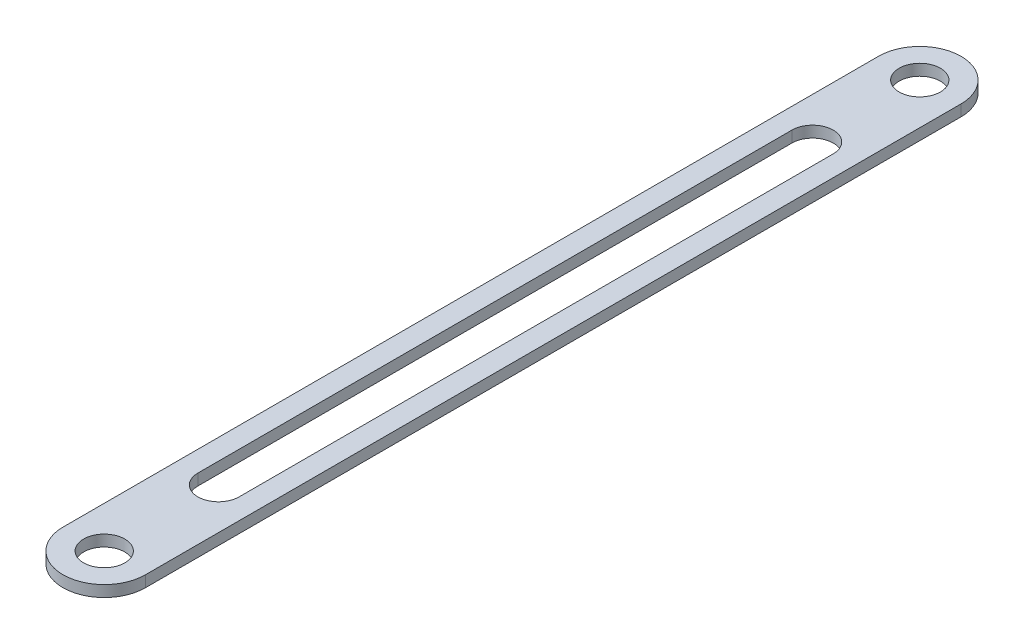
SolidWorks part; units mm, degrees
ref_plane "Front Plane" through (0, 0, 0) normal (0, 0, 1) x (1, 0, 0)
ref_plane "Top Plane" through (0, 0, 0) normal (0, 1, 0) x (1, 0, 0)
ref_plane "Right Plane" through (0, 0, 0) normal (1, 0, 0) x (0, 0, -1)
sketch "Sketch1" plane through (0, 0, 0) normal (0, 1, 0) x (1, 0, 0)
  line L0 (0, 100.4327) -> (0, -254.7867) construction
  line L1 (-11, 23.0454) -> (-11, -194.4046)
  line L2 (11, 23.0454) -> (11, -194.4046)
  line L3 (-67.2169, 0) -> (68.628, 0) construction
  line L4 (-5.5, -5.5346) -> (-5.5, -163.9346)
  line L5 (5.5, -5.5346) -> (5.5, -163.9346)
  arc A0 (-11, 23.0454) -> (11, 23.0454) centre (0, 23.0454) cw
  arc A1 (-11, -194.4046) -> (11, -194.4046) centre (0, -194.4046) ccw
  circle A2 centre (0, 23.0454) radius 5.5
  circle A3 centre (0, -194.4046) radius 5.5
  arc A4 (-5.5, -5.5346) -> (5.5, -5.5346) centre (0, -5.5346) cw
  arc A5 (-5.5, -163.9346) -> (5.5, -163.9346) centre (0, -163.9346) ccw
  point P19 (0, -0.0346)
  point P20 (0, -169.4346)
  dimension "D1" = 11
  dimension "D2" = 11
  dimension "D3" = 11
  dimension "D6" = 23.08
  dimension "D4" = 217.45
  dimension "D5" = 5.5
  dimension "D7" = 192.48
extrude "Boss-Extrude1" add sketch "Sketch1" along normal blind 3
